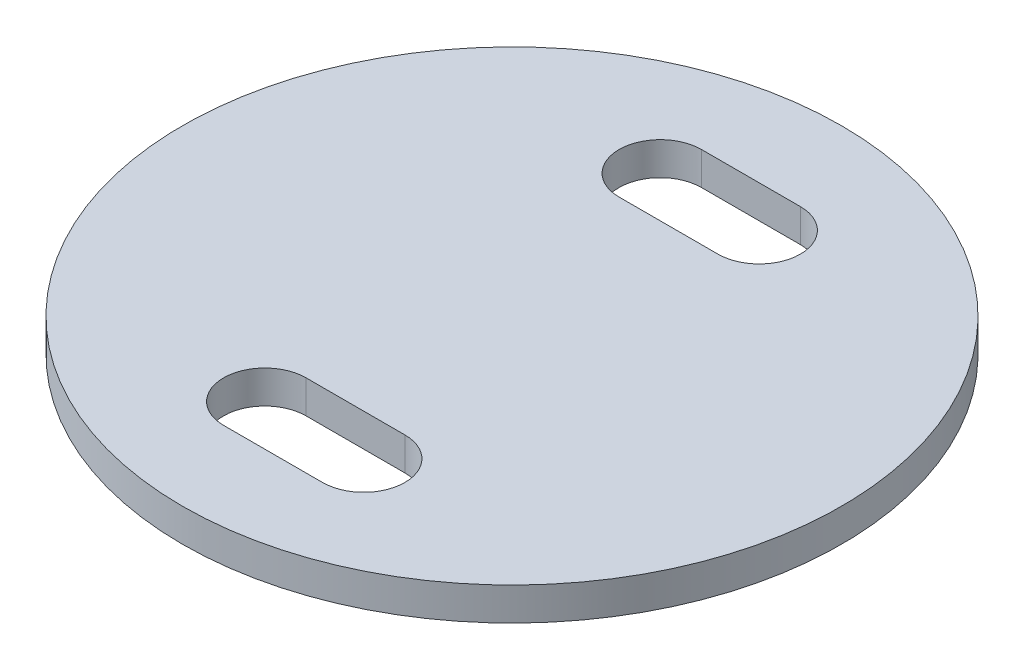
SolidWorks part; units mm, degrees
ref_plane "Front Plane" through (0, 0, 0) normal (0, 0, 1) x (1, 0, 0)
ref_plane "Top Plane" through (0, 0, 0) normal (0, 1, 0) x (1, 0, 0)
ref_plane "Right Plane" through (0, 0, 0) normal (1, 0, 0) x (0, 0, -1)
sketch "Sketch1" plane through (0, 0, 0) normal (0, 1, 0) x (1, 0, 0)
  circle A0 centre (0, 0) radius 100
  dimension "D1" = 200
extrude "Boss-Extrude1" add sketch "Sketch1" along normal blind 10
sketch "Sketch2" plane through (0, 10, 0) normal (0, 1, 0) x (1, 0, 0)
  line L0 (-15, -60) -> (15, -60) construction
  line L1 (-15, -47.5) -> (15, -47.5)
  line L2 (-15, -72.5) -> (15, -72.5)
  arc A0 (-15, -47.5) -> (-15, -72.5) centre (-15, -60) ccw
  arc A1 (15, -72.5) -> (15, -47.5) centre (15, -60) ccw
  point P2 (0, -60)
  dimension "D3" = 12.5
  dimension "D1" = 60
  dimension "D2" = 30
extrude "Cut-Extrude1" cut sketch "Sketch2" against normal through all
mirror "Mirror1" about plane through (0, 0, 0) normal (0, 0, 1) of "Cut-Extrude1"
